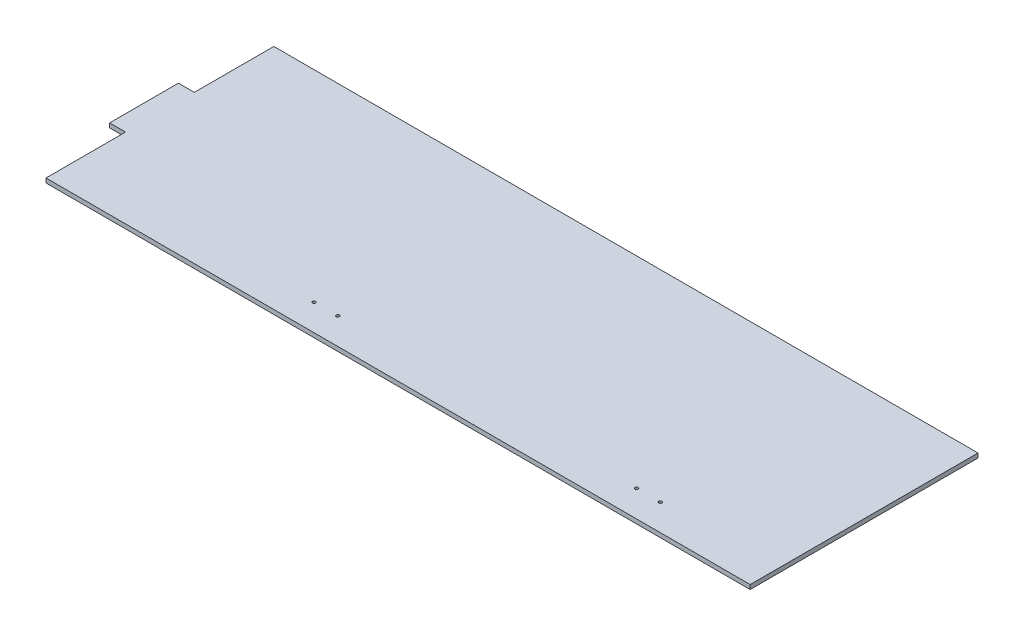
SolidWorks part; units mm, degrees
ref_plane "Front Plane" through (0, 0, 0) normal (0, 0, 1) x (1, 0, 0)
ref_plane "Top Plane" through (0, 0, 0) normal (0, 1, 0) x (1, 0, 0)
ref_plane "Right Plane" through (0, 0, 0) normal (1, 0, 0) x (0, 0, -1)
sketch "Sketch1" plane through (0, 0, 0) normal (0, 1, 0) x (1, 0, 0)
  line L0 (-280, 21.6257) -> (-270, 21.6257)
  line L1 (-270, 71.6257) -> (270, 71.6257)
  line L2 (-270, 71.6257) -> (-270, 21.6257)
  line L3 (-270, -71.6257) -> (270, -71.6257)
  line L4 (270, 71.6257) -> (270, -71.6257)
  line L5 (-270, 71.6257) -> (270, -71.6257) construction
  line L6 (-270, -71.6257) -> (270, 71.6257) construction
  line L7 (-280, 21.6257) -> (-280, -21.6257)
  line L8 (-280, -21.6257) -> (-270, -21.6257)
  line L9 (-270, -21.6257) -> (-270, -71.6257)
  line L10 (-270, 22.6702) -> (-270, 21.6257) construction
  line L11 (172.78, 71.6257) -> (172.78, -71.6257)
  line L13 (177.78, 62.3) -> (177.78, -62.3) construction
  circle A5 centre (99.6713, -54.974) radius 1 construction
  circle A6 centre (84.6713, -54.974) radius 1 construction
  circle A7 centre (-103.1287, -54.974) radius 1 construction
  circle A8 centre (-118.1287, -54.974) radius 1 construction
  circle A9 centre (99.6713, -54.974) radius 1
  circle A10 centre (84.6713, -54.974) radius 1
  circle A11 centre (-103.1287, -54.974) radius 1
  circle A12 centre (-118.1287, -54.974) radius 1
  point P4 (0, 0)
  point P17 (0, 0)
  point P27 (0, 0)
  dimension "D1" = 50
  dimension "D2" = 50
  dimension "D3" = 5
  dimension "D6" = 10
  dimension "D7" = 540
  dimension "D8" = 143.2513
extrude "Boss-Extrude1" add sketch "Sketch1" along normal blind 2.7432 from offset 2 contours L8 L9 L3 L4 L1 L2 L0 L7 region at (-50.1513, 0, -0.0108)
